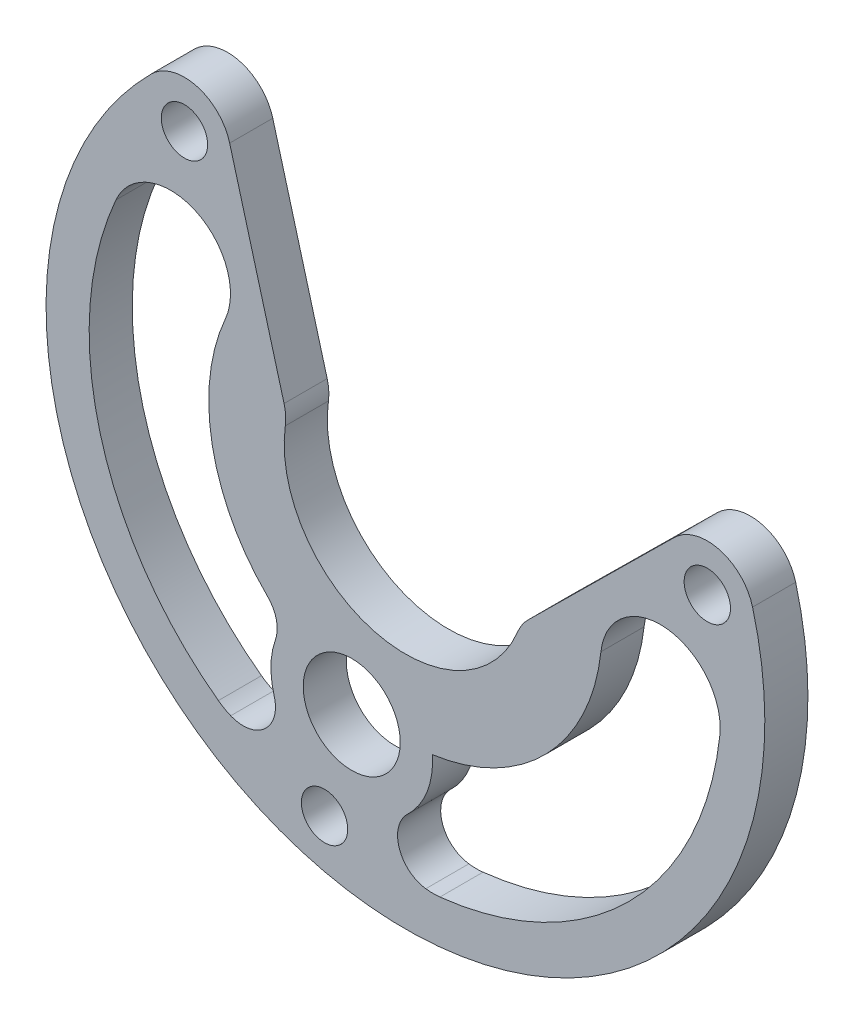
SolidWorks part; units mm, degrees
material "6061 Alloy"
ref_plane "Front Plane" through (0, 0, 0) normal (0, 0, 1) x (1, 0, 0)
ref_plane "Top Plane" through (0, 0, 0) normal (0, 1, 0) x (1, 0, 0)
ref_plane "Right Plane" through (0, 0, 0) normal (1, 0, 0) x (0, 0, -1)
sketch "Sketch1" plane through (0, 0, 0) normal (0, 0, 1) x (1, 0, 0)
  line L0 (169.0712, 34.6) -> (155.4979, 21.1875)
  line L1 (132.8544, 27.2548) -> (127.8058, 45.657)
  line L2 (144.1169, 24) -> (173.1367, 52.6759) construction
  arc A0 (177.4669, 23.9998) -> (120.5529, 47.6) centre (144.1169, 24) ccw construction
  arc A1 (120.5349, 47.582) -> (176.3305, 32.6316) centre (144.1169, 24) ccw
  circle A2 centre (136.6111, -4.0118) radius 2.15 construction
  circle A3 centre (172.1287, 31.5058) radius 2.15 construction
  circle A4 centre (123.6108, 44.5061) radius 2.15 construction
  circle A5 centre (144.1169, 24) radius 11.25 construction
  arc A6 (146.1075, 5.8589) -> (147.3182, -5.1749) centre (146.7128, 0.342) ccw construction
  arc A7 (147.3182, -5.1749) -> (173.2918, 20.7987) centre (144.1169, 24) ccw construction
  arc A8 (146.1075, 5.8589) -> (162.258, 22.0094) centre (144.1169, 24) ccw construction
  arc A9 (173.2918, 20.7987) -> (162.258, 22.0094) centre (167.7749, 21.4041) ccw construction
  arc A10 (126.757, 0.3344) -> (133.3224, 9.2846) centre (130.0397, 4.8095) ccw construction
  arc A11 (117.25, 35.8151) -> (126.757, 0.3344) centre (144.1169, 24) ccw construction
  arc A12 (127.4109, 31.3467) -> (133.3224, 9.2846) centre (144.1169, 24) ccw construction
  arc A13 (127.4109, 31.3467) -> (117.25, 35.8151) centre (122.3305, 33.5809) ccw construction
  arc A14 (127.4109, 31.3467) -> (117.25, 35.8151) centre (122.3305, 33.5809) ccw
  arc A15 (127.4109, 31.3467) -> (133.3224, 9.2846) centre (144.1169, 24) ccw
  arc A16 (117.25, 35.8151) -> (126.757, 0.3344) centre (144.1169, 24) ccw
  arc A17 (126.757, 0.3344) -> (133.3224, 9.2846) centre (130.0397, 4.8095) ccw
  arc A18 (173.2918, 20.7987) -> (162.258, 22.0094) centre (167.7749, 21.4041) ccw
  arc A19 (146.1075, 5.8589) -> (162.258, 22.0094) centre (144.1169, 24) ccw
  arc A20 (147.3182, -5.1749) -> (173.2918, 20.7987) centre (144.1169, 24) ccw
  arc A21 (146.1075, 5.8589) -> (147.3182, -5.1749) centre (146.7128, 0.342) ccw
  arc A22 (132.9697, 25.5173) -> (154.5293, 19.7404) centre (144.1169, 24) ccw
  circle A23 centre (123.6108, 44.5061) radius 2.15
  circle A24 centre (172.1287, 31.5058) radius 2.15
  circle A25 centre (136.6111, -4.0118) radius 2.15
  arc A26 (176.3305, 32.6316) -> (169.0712, 34.6) centre (172.1287, 31.5058) ccw
  arc A27 (155.4979, 21.1875) -> (154.5293, 19.7404) centre (158.5554, 18.0933) ccw
  arc A28 (132.9697, 25.5173) -> (132.8544, 27.2548) centre (128.6594, 26.104) ccw
  arc A29 (120.5349, 47.582) -> (127.8058, 45.657) centre (123.6108, 44.5061) cw
  dimension "D1" = 10
extrude "Boss-Extrude1" add sketch "Sketch1" along normal blind 4
sketch "Sketch2" plane through (0, 0, 0) normal (0, 0, -1) x (-1, 0, 0)
  circle A0 centre (-139.1346, 5.4059) radius 4.5
  dimension "D1" = 9
extrude "Cut-Extrude1" cut sketch "Sketch2" against normal blind 10
sketch "Sketch3" plane through (0, 0, 4) normal (0, 0, 1) x (1, 0, 0)
  arc A0 (143.6109, 4.9442) -> (135.0272, 7.2442) centre (139.1346, 5.4059) ccw construction
  circle A1 centre (139.1346, 5.4059) radius 4.5
  circle A2 centre (139.1346, 5.4059) radius 7.5
  dimension "D1" = 15
extrude "Boss-Extrude2" add sketch "Sketch3" against normal blind 4
fillet "Fillet1" radius 3 3 edges at (133.4927, 0.4644, 2) (132.9129, 9.594, 2) (141.5499, -1.6945, 2)
